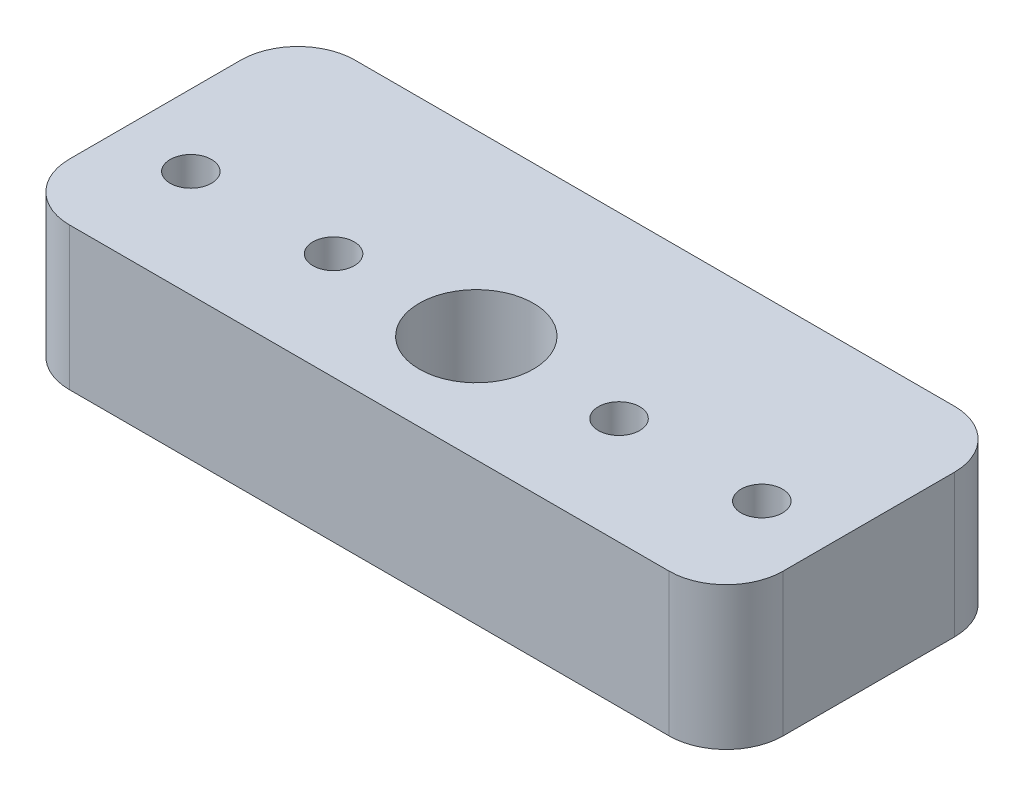
SolidWorks part; units mm, degrees
ref_plane "Front Plane" through (0, 0, 0) normal (0, 0, 1) x (1, 0, 0)
ref_plane "Top Plane" through (0, 0, 0) normal (0, 1, 0) x (1, 0, 0)
ref_plane "Right Plane" through (0, 0, 0) normal (1, 0, 0) x (0, 0, -1)
sketch "Sketch1" plane through (0, 0, 0) normal (0, 1, 0) x (1, 0, 0)
  line L0 (-25, -2.5) -> (25, -2.5) construction
  line L1 (-21, 10) -> (21, 10)
  line L2 (-25, 6) -> (-25, -6)
  line L3 (-21, -10) -> (21, -10)
  line L4 (25, 6) -> (25, -6)
  line L5 (-25, 10) -> (25, -10) construction
  line L6 (-25, -10) -> (25, 10) construction
  line L7 (0, -10) -> (0, 10) construction
  line L8 (25, 10) -> (-25, -10) construction
  arc A0 (-25, -6) -> (-21, -10) centre (-21, -6) ccw
  arc A1 (21, -10) -> (25, -6) centre (21, -6) ccw
  arc A2 (21, 10) -> (25, 6) centre (21, 6) cw
  arc A3 (-21, 10) -> (-25, 6) centre (-21, 6) ccw
  circle A4 centre (0, -2.5) radius 4
  circle A5 centre (10, -2.5) radius 1.45
  circle A6 centre (20, -2.5) radius 1.45
  circle A7 centre (-20, -2.5) radius 1.45
  circle A8 centre (-10, -2.5) radius 1.45
  point P0 (0, 0)
  dimension "D3" = 4
  dimension "D4" = 8
  dimension "D5" = 2.9
  dimension "D6" = 2.9
  dimension "D1" = 20
  dimension "D7" = 7.5
  dimension "D8" = 10
  dimension "D9" = 40
  dimension "D2" = 5
extrude "Boss-Extrude1" add sketch "Sketch1" along normal blind 10
equation "\"Y-ROD-SPACING\"=75"
equation "\"Y-BED-OFFSET\"=2"
equation "\"Y-BED-ROD-INSET\"=3.5"
equation "\"T-SLOT-NUT-FILLET-RADIUS\"=0.5"
equation "\"T-SLOT-SCREW-SHAFT-RADIUS\"=1.55"
equation "\"T-SLOT-SCREW-SHAFT-CUTOUT-LENGTH\"=11"
equation "\"T-SLOT-NUT-DEPTH\"=3.5"
equation "\"T-SLOT-NUT-WIDTH\"=2.85"
equation "\"T-SLOT-NUT-END-DISTANCE\"=8"
equation "\"ACRYLIC-TAB-CUTOUT-SIZE\"=\"ACRYLIC-THICKNESS\"+\"ACRYLIC-TAB-TOLERANCE\"*2"
equation "\"ACRYLIC-M3-HOLE\"=2.9"
equation "\"SMOOTHROD-CAP-SCREW-DISTANCE\"=20"
equation "\"D5@Sketch1\"=\"ACRYLIC-M3-HOLE\""
equation "\"D6@Sketch1\"=\"ACRYLIC-M3-HOLE\""
equation "\"D8@Sketch1\"=\"SMOOTHROD-CAP-SCREW-DISTANCE\"/2"
equation "\"ACRYLIC-TAB-WIDTH\"=\"ACRYLIC-THICKNESS\""
equation "\"FRAME-WIDTH-INNER\"=370"
equation "\"NEMA17-HOLE-SPACING\"=31"
equation "\"NEMA17-CENTRAL-CUTOUT\"=22.5"
equation "\"Z-BRACKET-REACH\"=55"
equation "\"TOP-BRACKET-SPACING\"=40"
equation "\"D9@Sketch1\"=\"TOP-BRACKET-SPACING\""
equation "\"D2@Sketch1\"=\"ACRYLIC-TAB-WIDTH\"/2"
equation "\"X-ROD-SPACING\"=45"
equation "\"Z-ROD-SPACING\"=17.5"
equation "\"ACRYLIC-THICKNESS\"=10"
equation "\"ACRYLIC-THICKNESS2\"=4.5"
equation "\"SMOOTHROD-X-LENGTH\"=350"
equation "\"SMOOTHROD-Y-LENGTH\"=350"
equation "\"SMOOTHROD-Z-LENGTH\"=350"
equation "\"SMOOTHROD-TIGHTENING-HEADROOM\"=.25"
equation "\"LEADSCREW-Z-LENGTH\"=300"
equation "\"SCREW-LENGTH-FRAME\"=\"ACRYLIC-THICKNESS\" + 10"
equation "\"SCREW-HEAD-RADIUS\"=6"
equation "\"PRINTED-X-SMOOTHROD-DIAMETER\"=9.0"
equation "\"PRINTED-X-SMOOTHROD-CUTOUT\"=10"
equation "\"PRINTED-X-BASE-HEIGHT\"=10"
equation "\"PRINTED-LM8UU-CUTOUT-SIZE\"=15.5"
equation "\"PRINTED-LM8UU-CUTOUT-LENGTH\"=24.5"
equation "\"PRINTED-X-IDLER-HEIGHT\"=16"
equation "\"PSU-MOUNTING-WIDTH\"=95"
equation "\"PSU-MOUNTING-HEIGHT\"=177"
equation "\"D1@Boss-Extrude1\"=\"ACRYLIC-THICKNESS\""
